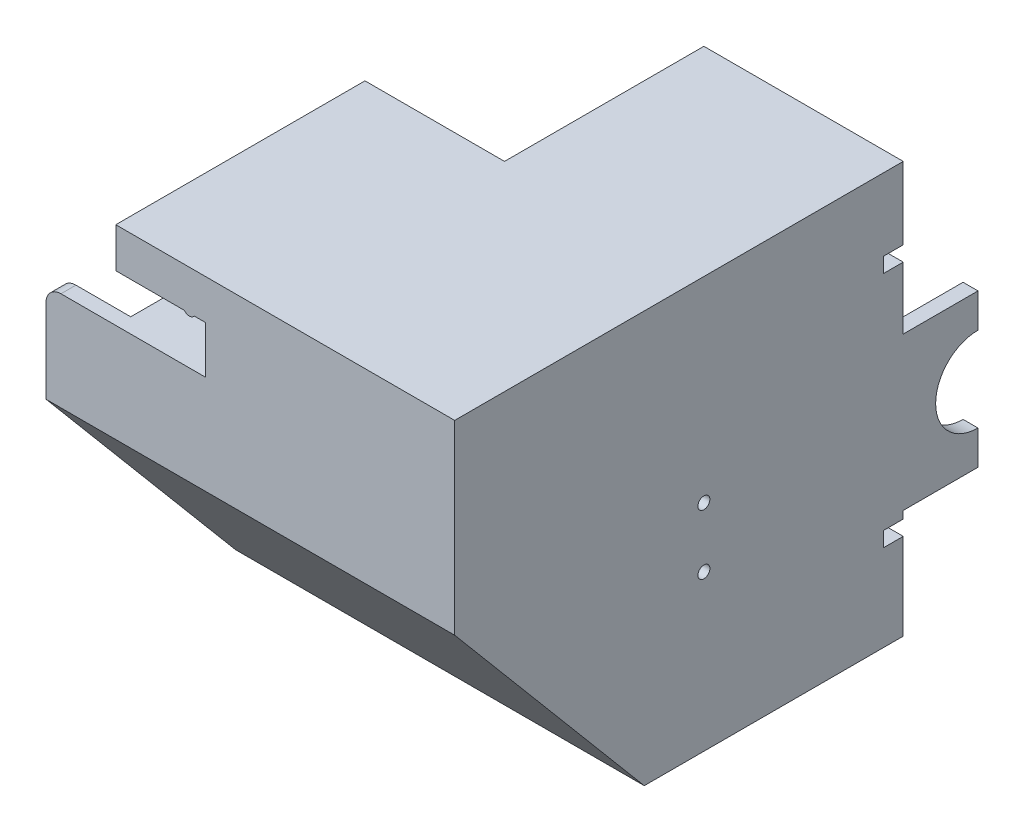
SolidWorks part; units mm, degrees
ref_plane "Front Plane" through (0, 0, 0) normal (0, 0, 1) x (1, 0, 0)
ref_plane "Top Plane" through (0, 0, 0) normal (0, 1, 0) x (1, 0, 0)
ref_plane "Right Plane" through (0, 0, 0) normal (1, 0, 0) x (0, 0, -1)
sketch "Sketch1" plane through (0, 0, 75.0548) normal (0, 0, 1) x (1, 0, 0)
  line L0 (-69.2126, 51.9708) -> (-97.2126, 51.9708)
  line L1 (-97.2126, 51.9708) -> (-97.2126, 43.9708)
  line L2 (-97.2126, 43.9708) -> (-83.4626, 43.9708)
  line L3 (-81.4626, 43.9708) -> (-79.2126, 43.9708)
  line L4 (-79.2126, 43.9708) -> (-79.2126, 34.4708)
  line L5 (-79.2126, 34.4708) -> (-97.2126, 34.4708)
  line L6 (-97.2126, 34.4708) -> (-97.2126, 26.4708)
  line L7 (-97.2126, 26.4708) -> (-69.2126, 26.4708)
  line L8 (-69.2126, 26.4708) -> (-69.2126, 51.9708)
  arc A0 (-83.4626, 43.9708) -> (-81.4626, 43.9708) centre (-82.4626, 44.7208) ccw
  arc A1 (-83.4626, 43.9708) -> (-81.4626, 43.9708) centre (-82.4626, 44.7208) ccw construction
  arc M1 (-83.4626, 43.9708) -> (-81.4626, 43.9708) centre (-82.4626, 44.7208) ccw
  line M2 (-81.4626, 43.9708) -> (-79.2126, 43.9708)
  line M3 (-79.2126, 43.9708) -> (-79.2126, 34.4708)
  line M4 (-79.2126, 34.4708) -> (-97.2126, 34.4708)
  line M5 (-97.2126, 34.4708) -> (-97.2126, 26.4708)
  line M6 (-97.2126, 26.4708) -> (-69.2126, 26.4708)
  line M7 (-69.2126, 26.4708) -> (-69.2126, 51.9708)
  line M8 (-69.2126, 51.9708) -> (-97.2126, 51.9708)
  line M9 (-97.2126, 51.9708) -> (-97.2126, 43.9708)
  line M10 (-97.2126, 43.9708) -> (-83.4626, 43.9708)
extrude "Boss-Extrude1" add sketch "Sketch1" along normal blind 50 contours M10 M1 M2 M3 M4 M5 M6 M7 M8 M9 region at (-69.5913, 39.2208, 75.0548)
sketch "Sketch2" plane through (-69.2126, 0, 0) normal (1, 0, 0) x (0, 0, -1)
  line L0 (-125.0548, 51.9708) -> (-35.0548, 51.9708)
  line L1 (-35.0548, 51.9708) -> (-35.0548, 48.9708)
  line L2 (-35.0548, 22.4708) -> (-35.0548, 51.9708) construction
  line L3 (-35.0548, 48.9708) -> (-125.0548, 48.9708)
  line L4 (-125.0548, 26.4708) -> (-125.0548, 51.9708) construction
  line L5 (-125.0548, 48.9708) -> (-125.0548, 51.9708)
  line L6 (-125.0548, 48.9708) -> (-125.0548, 26.4708)
  line L7 (-125.0548, 26.4708) -> (-122.0548, 26.4708)
  line L8 (-125.0548, 26.4708) -> (-75.0548, 26.4708) construction
  line L9 (-122.0548, 26.4708) -> (-122.0548, 48.9708)
  line M3 (-75.0548, 26.4708) -> (-75.0548, 51.9708)
  line M4 (-75.0548, 51.9708) -> (-125.0548, 51.9708)
  line M5 (-125.0548, 51.9708) -> (-125.0548, 26.4708)
  line M6 (-125.0548, 26.4708) -> (-75.0548, 26.4708)
  dimension "D1" = 3
  dimension "D2" = 3
extrude "Boss-Extrude2" add sketch "Sketch2" along normal up to surface (40 mm away) contours L9 L3 M6 M5 | L3 M3 M4 M5 | L3 L1 L0 M3 region at (-69.2126, 50.4708, 100.0548) region at (-69.2126, 50.4708, 55.0548) region at (-69.2126, 37.7208, 123.5548)
sketch "Sketch3" plane through (0, 0, 75.0548) normal (0, 0, -1) x (-1, 0, 0)
  line L0 (79.2126, 43.9708) -> (97.2126, 43.9708)
  line L1 (97.2126, 43.9708) -> (97.2126, 34.4708)
  line L2 (97.2126, 34.4708) -> (79.2126, 34.4708)
  line L3 (79.2126, 34.4708) -> (79.2126, 43.9708)
extrude "Cut-Extrude1" cut sketch "Sketch3" against normal blind 30
sketch "Sketch4" plane through (0, 48.9708, 0) normal (0, -1, 0) x (1, 0, 0)
  line L0 (-29.2126, 125.0548) -> (-32.2126, 125.0548)
  line L1 (-97.2126, 125.0548) -> (-29.2126, 125.0548) construction
  line L2 (-32.2126, 125.0548) -> (-32.2126, 35.0548)
  line L3 (-29.2126, 35.0548) -> (-69.2126, 35.0548) construction
  line L4 (-32.2126, 35.0548) -> (-29.2126, 35.0548)
  line L5 (-29.2126, 35.0548) -> (-29.2126, 125.0548)
  dimension "D1" = 3
extrude "Boss-Extrude3" add sketch "Sketch4" along normal up to surface (79.5 mm away)
sketch "Sketch6" plane through (-32.2126, 0, 0) normal (-1, 0, 0) x (0, 0, 1)
  line L0 (125.0548, -30.5292) -> (35.0548, -30.5292)
  line L1 (35.0548, -30.5292) -> (35.0548, -27.5292)
  line L2 (35.0548, -30.5292) -> (35.0548, 48.9708) construction
  line L3 (35.0548, -27.5292) -> (125.0548, -27.5292)
  line L4 (125.0548, -30.5292) -> (125.0548, 26.4708) construction
  line L5 (125.0548, -27.5292) -> (125.0548, -30.5292)
  dimension "D1" = 3
extrude "Boss-Extrude4" add sketch "Sketch6" along normal up to surface (79 mm away)
sketch "Sketch7" plane through (0, 0, 125.0548) normal (0, 0, 1) x (1, 0, 0)
  line L0 (-111.2126, -27.5292) -> (-32.2126, -27.5292)
  line L1 (-32.2126, -27.5292) -> (-32.2126, 26.4708)
  line L2 (-32.2126, 26.4708) -> (-97.2126, 26.4708)
  line L3 (-97.2126, 26.4708) -> (-97.2126, 34.4708)
  line L4 (-97.2126, 34.4708) -> (-111.2126, 34.4708)
  line L5 (-111.2126, 34.4708) -> (-111.2126, -27.5292)
extrude "Boss-Extrude5" add sketch "Sketch7" against normal blind 3
fillet "Fillet1" radius 3 1 edges at (-111.2126, 34.4708, 123.5548)
sketch "Sketch11" plane through (-29.2126, 0, 0) normal (1, 0, 0) x (0, 0, -1)
  line L0 (-35.0548, 34.4708) -> (-39.0548, 34.4708)
  line L1 (-35.0548, 51.9708) -> (-35.0548, -30.5292) construction
  line L2 (-35.0548, 28.4708) -> (-35.0548, 34.4708) construction
  line L3 (-39.0548, 34.4708) -> (-39.0548, 37.4708)
  line L4 (-39.0548, 37.4708) -> (-35.0548, 37.4708)
  line L5 (-35.0548, 37.4708) -> (-35.0548, 34.4708)
  line L6 (-75.0548, 34.4708) -> (-25.0548, 34.4708) construction
  dimension "D1" = 3
  dimension "D2" = 4
extrude "Cut-Extrude2" cut sketch "Sketch11" against normal up to surface (3 mm away) up to face at (-32.2126, 10.7208, 78.5548)
sketch "Sketch12" plane through (0, -30.5292, 0) normal (0, -1, 0) x (1, 0, 0)
  line L0 (-111.2126, 35.0548) -> (-29.2126, 35.0548)
  line L1 (-69.2126, 35.0548) -> (-69.2126, 75.0548)
  line L2 (-70.7126, 39.0548) -> (-67.7126, 39.0548)
  line L3 (-67.7126, 39.0548) -> (-67.7126, 35.0548)
  line L4 (-67.7126, 35.0548) -> (-70.7126, 35.0548)
  line L5 (-70.7126, 35.0548) -> (-70.7126, 39.0548)
  line L6 (-75.2126, 75.0548) -> (-63.2126, 75.0548)
  circle A0 centre (-75.2126, 75.0548) radius 1.2
  circle A1 centre (-63.2126, 75.0548) radius 1.2
  point P10 (-69.2126, 39.0548)
  point P14 (-69.2126, 75.0548)
  dimension "D5" = 2.4
  dimension "D6" = 2.4
  dimension "D1" = 40
  dimension "D2" = 4
  dimension "D3" = 3
  dimension "D4" = 12
sketch "Sketch13" plane through (-29.2126, 0, 0) normal (1, 0, 0) x (0, 0, -1)
  line L0 (-5.0548, 22.4708) -> (-5.0548, -9.1792)
  line L1 (-5.0548, 6.6458) -> (-20.0548, 6.6458)
  line L2 (-5.0548, 22.4708) -> (-35.0548, 22.4708)
  line L3 (-35.0548, 22.4708) -> (-35.0548, -9.1792)
  line L4 (-35.0548, -9.1792) -> (-5.0548, -9.1792)
  line L5 (-20.0548, -9.1792) -> (-20.0548, 22.4708)
  line L6 (-20.0548, 21.9708) -> (-35.0548, 21.9708)
  line L7 (-20.0548, -8.6792) -> (-35.0548, -8.6792)
  circle A0 centre (-20.0548, 6.6458) radius 8.5
  point P9 (-20.0548, 6.6458)
  point P16 (-5.0548, 22.4708)
  dimension "D1" = 17
  dimension "D2" = 15
  dimension "D3" = 0.5
  dimension "D4" = 0.5
extrude "Boss-Extrude6" add sketch "Sketch13" against normal blind 3 contours A0 L5 L6 L3 L7 region at (-29.2126, 6.6458, 28.8306)
sketch "Sketch15" plane through (-29.2126, 0, 0) normal (1, 0, 0) x (0, 0, -1)
  line L0 (-35.0548, 22.4708) -> (-35.0548, -9.1792) construction
  line L1 (-35.0548, 6.6458) -> (-75.0548, 6.6458)
  line L6 (-75.0548, 0.6458) -> (-75.0548, 12.6458)
  line L7 (-35.0548, -10.1792) -> (-39.0548, -10.1792)
  line L8 (-35.0548, -8.6792) -> (-35.0548, -30.5292) construction
  line L9 (-39.0548, -10.1792) -> (-39.0548, -13.1792)
  line L10 (-39.0548, -13.1792) -> (-35.0548, -13.1792)
  line L11 (-35.0548, -13.1792) -> (-35.0548, -10.1792)
  line L12 (-20.0548, -8.6792) -> (-35.0548, -8.6792) construction
  circle A0 centre (-75.0548, 0.6458) radius 1.2
  circle A1 centre (-75.0548, 12.6458) radius 1.2
  point P9 (-35.0548, -10.2764)
  point P11 (-75.0548, 6.6458)
  line M13 (-35.0548, -30.5292) -> (-35.0548, -8.6792)
  dimension "D2" = 2.4
  dimension "D3" = 2.4
  dimension "D1" = 12
  dimension "D4" = 40
  dimension "D5" = 3
  dimension "D6" = 4
  dimension "D7" = 1.5
extrude "Cut-Extrude3" cut sketch "Sketch15" against normal up to surface (3 mm away) contours L9 L10 L7 M13 | A0 | A1 region at (-29.2126, 13.4703, 75.8794) region at (-29.2126, 1.4703, 74.2303) region at (-29.2126, -11.6792, 37.0548) up to face at (-32.2126, 16.1886, 44.3763)
sketch "Sketch16" plane through (-29.2126, 0, 0) normal (1, 0, 0) x (0, 0, -1)
  line L0 (-125.0548, 16.9708) -> (-85.0548, -30.5292)
  line L1 (-125.0548, 51.9708) -> (-125.0548, -30.5292) construction
  line L2 (-125.0548, -30.5292) -> (-35.0548, -30.5292) construction
  line L3 (-85.0548, -30.5292) -> (-125.0548, -30.5292)
  line L4 (-125.0548, -30.5292) -> (-125.0548, 16.9708)
  line L5 (-35.0548, 51.9708) -> (-125.0548, 51.9708) construction
  dimension "D1" = 35
  dimension "D2" = 40
extrude "Cut-Extrude4" cut sketch "Sketch16" against normal through all
sketch "Sketch17" plane through (-29.2126, 0, 0) normal (1, 0, 0) x (0, 0, -1)
  line L0 (-125.0548, 19.2995) -> (-125.0548, 14.6421)
  line L1 (-125.0548, 14.6421) -> (-87.0158, -30.5292)
  line L2 (-87.0158, -30.5292) -> (-83.0938, -30.5292)
  line L3 (-83.0938, -30.5292) -> (-125.0548, 19.2995)
  point P2 (-85.0548, -30.5292)
  point P4 (-125.0548, 16.9708)
  dimension "D1" = 3
extrude "Boss-Extrude7" add sketch "Sketch17" against normal up to surface (82 mm away) up to face at (-111.2126, -29.0292, 60.6864)
